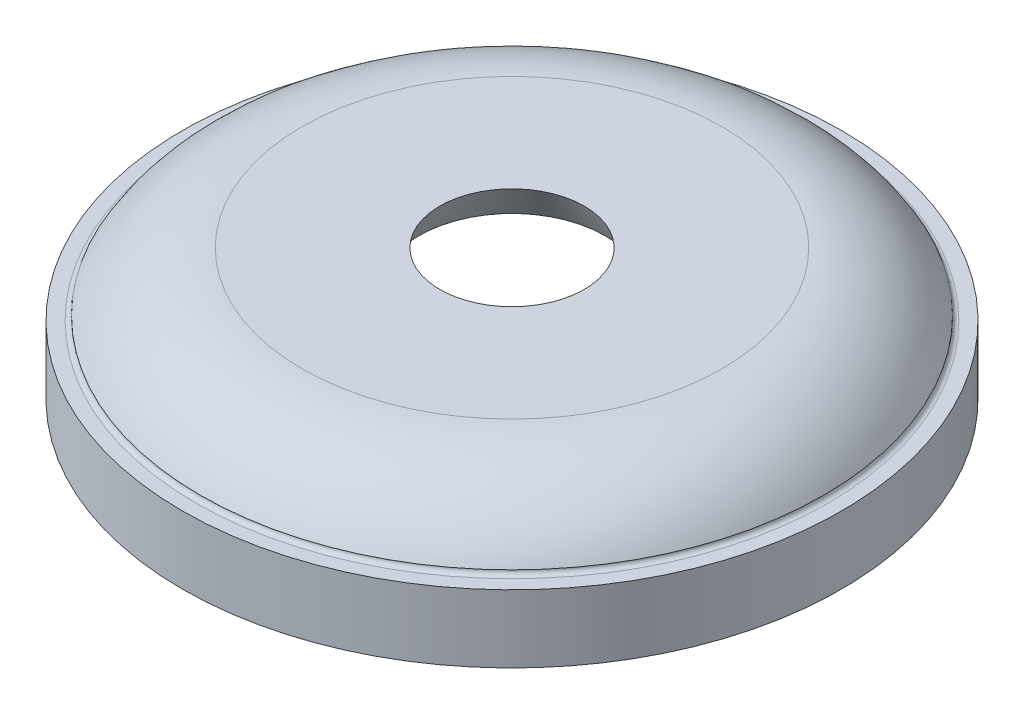
SolidWorks part; units mm, degrees
material "Silica Phenolic"
ref_plane "Piano frontale" through (0, 0, 0) normal (0, 0, 1) x (1, 0, 0)
ref_plane "Piano superiore" through (0, 0, 0) normal (0, 1, 0) x (1, 0, 0)
ref_plane "Piano destro" through (0, 0, 0) normal (1, 0, 0) x (0, 0, -1)
sketch "Schizzo1" plane through (0, 0, 0) normal (0, 0, 1) x (1, 0, 0)
  line L0 (-71, 0) -> (-73, 0)
  line L1 (-73, 0) -> (-73, 15)
  line L2 (-71, 0) -> (-71, 3)
  line L3 (-71, 3) -> (-69, 3)
  line L4 (-46.4833, 21) -> (-20.6188, 21)
  line L5 (-20.6188, 21) -> (-16, 29)
  line L6 (-16, 29) -> (-46.4833, 29)
  line L7 (0, 0) -> (0, 32.2434) construction
  line L9 (-73, 15) -> (-69, 15)
  line L10 (-69, 15) -> (-69, 16)
  line L11 (-46.4833, 21) -> (-46.4833, 29) construction
  line L13 (69, 16) -> (-69, 16) construction
  line L14 (-69, 3) -> (-68.0743, 5.6575)
  arc A3 (-69, 16) -> (-46.4833, 29) centre (-46.4833, 3) cw
  arc A5 (-53.6248, 28) -> (-69, 16) centre (-46.4833, 3) ccw construction
  arc A6 (-68.0743, 5.6575) -> (-46.4833, 21) centre (-46.4833, -1.8633) cw
  point P14 (0, 0)
  dimension "D3" = 3
  dimension "D4" = 30
  dimension "D1" = 8
  dimension "D2" = 4
  dimension "D5" = 146
  dimension "D6" = 32
  dimension "D7" = 29
  dimension "D8" = 15
revolve "Rivoluzione1" add sketch "Schizzo1" angle 360 about L7
fillet "Raccordo1" radius 1 1 edges at (0, 15, -69)
